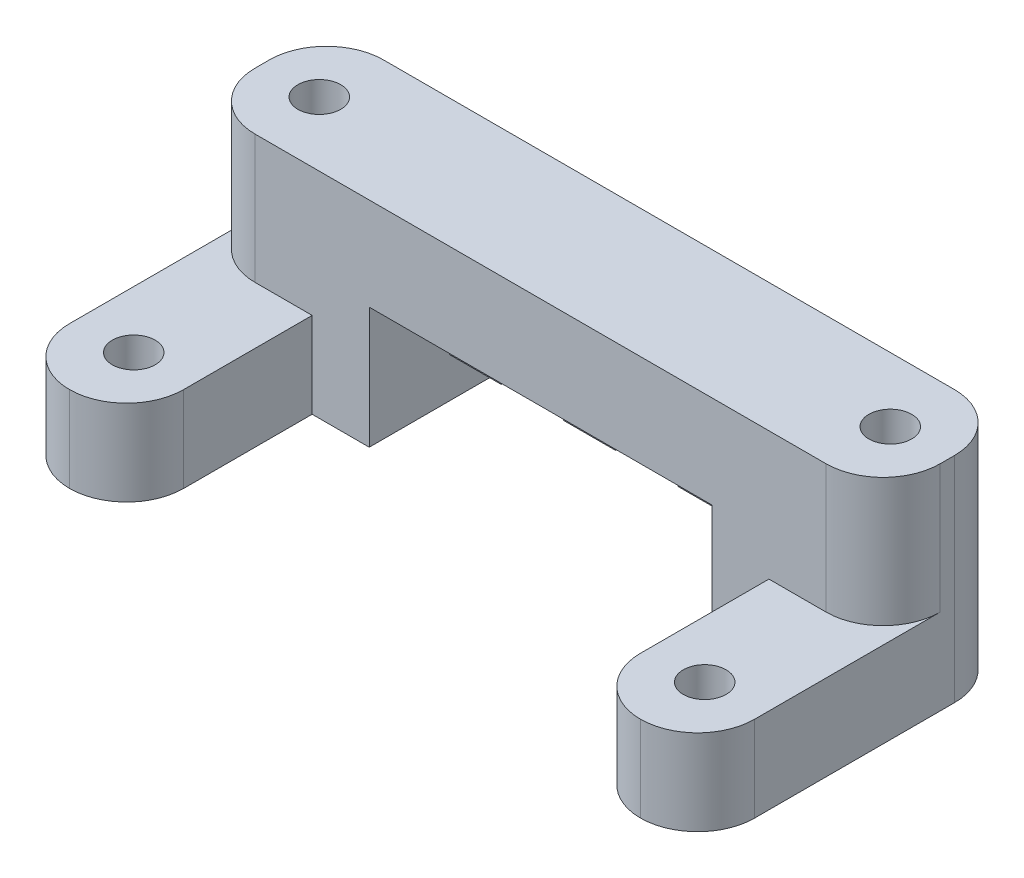
SolidWorks part; units mm, degrees
ref_plane "Front Plane" through (0, 0, 0) normal (0, 0, 1) x (1, 0, 0)
ref_plane "Top Plane" through (0, 0, 0) normal (0, 1, 0) x (1, 0, 0)
ref_plane "Right Plane" through (0, 0, 0) normal (1, 0, 0) x (0, 0, -1)
sketch "Sketch1" plane through (0, 0, 0) normal (0, 0, 1) x (1, 0, 0)
  line L0 (0, 0) -> (12, 0)
  line L1 (12, 0) -> (12, 8.5)
  line L2 (12, 8.5) -> (36, 8.5)
  line L3 (36, 8.5) -> (36, 0)
  line L4 (36, 0) -> (48, 0)
  line L5 (48, 0) -> (48, 15)
  line L8 (48, 15) -> (0, 15)
  line L11 (0, 15) -> (0, 0)
  point P3 (24, 8.5)
  point P13 (24, 15)
  dimension "D1" = 8.5
  dimension "D2" = 24
  dimension "D3" = 12
  dimension "D4" = 15
extrude "Boss-Extrude1" add sketch "Sketch1" along normal blind 9
sketch "Sketch2" plane through (0, 8.5, 0) normal (0, -1, 0) x (-1, 0, 0)
  line L0 (-12, -9) -> (-12, 0) construction
  line L1 (-14, -5.75) -> (-18, -5.75)
  line L2 (-14, -5.75) -> (-14, -3.25)
  line L3 (-14, -3.25) -> (-18, -3.25)
  line L4 (-18, -5.75) -> (-18, -3.25)
  line L5 (-22, -5.75) -> (-26, -5.75)
  line L6 (-22, -5.75) -> (-22, -3.25)
  line L7 (-22, -3.25) -> (-26, -3.25)
  line L8 (-26, -5.75) -> (-26, -3.25)
  line L9 (-30, -5.75) -> (-34, -5.75)
  line L10 (-30, -5.75) -> (-30, -3.25)
  line L11 (-30, -3.25) -> (-34, -3.25)
  line L12 (-34, -5.75) -> (-34, -3.25)
  point P12 (-16, -5.75)
  point P13 (-24, -5.75)
  point P14 (-32, -5.75)
  point P15 (-34, -4.5)
  point P16 (-26, -4.5)
  point P17 (-18, -4.5)
  point P20 (-12, -4.5)
  point P21 (-14, -4.5)
  dimension "D1" = 4
  dimension "D2" = 2.5
  dimension "D3" = 4
  dimension "D4" = 2.5
  dimension "D5" = 4
  dimension "D6" = 2.5
  dimension "D7" = 8
  dimension "D8" = 8
  dimension "D9" = 4
extrude "Boss-Extrude2" add sketch "Sketch2" along normal blind 3.5 draft 3
sketch "Sketch4" plane through (0, 0, 9) normal (0, 0, 1) x (1, 0, 0)
  line L1 (0, 0) -> (8, 0)
  line L2 (0, 0) -> (0, 6)
  line L3 (0, 6) -> (8, 6)
  line L4 (8, 0) -> (8, 6)
  line L5 (48, 0) -> (40, 0)
  line L6 (48, 0) -> (48, 6)
  line L7 (48, 6) -> (40, 6)
  line L8 (40, 0) -> (40, 6)
  dimension "D1" = 6
  dimension "D2" = 8
  dimension "D3" = 8
extrude "Boss-Extrude4" add sketch "Sketch4" along normal blind 13
sketch "Sketch3" plane through (0, 15, 0) normal (0, 1, 0) x (1, 0, 0)
  line L2 (8, -22) -> (0, -22) construction
  circle A0 centre (4, -4.5) radius 1.5
  circle A1 centre (44, -4.5) radius 1.5
  circle A2 centre (4, -17.5) radius 1.5
  circle A3 centre (44, -17.5) radius 1.5
  point P9 (4, -22)
  dimension "D2" = 3
  dimension "D1" = 40
  dimension "D3" = 13
extrude "Cut-Extrude1" cut sketch "Sketch3" against normal through all
fillet "Fillet1" radius 4 8 edges at (40, 3, 22) (48, 3, 22) (48, 7.5, 0) (48, 10.5, 9) (0, 3, 22) (8, 3, 22) (0, 7.5, 0) (0, 10.5, 9)
